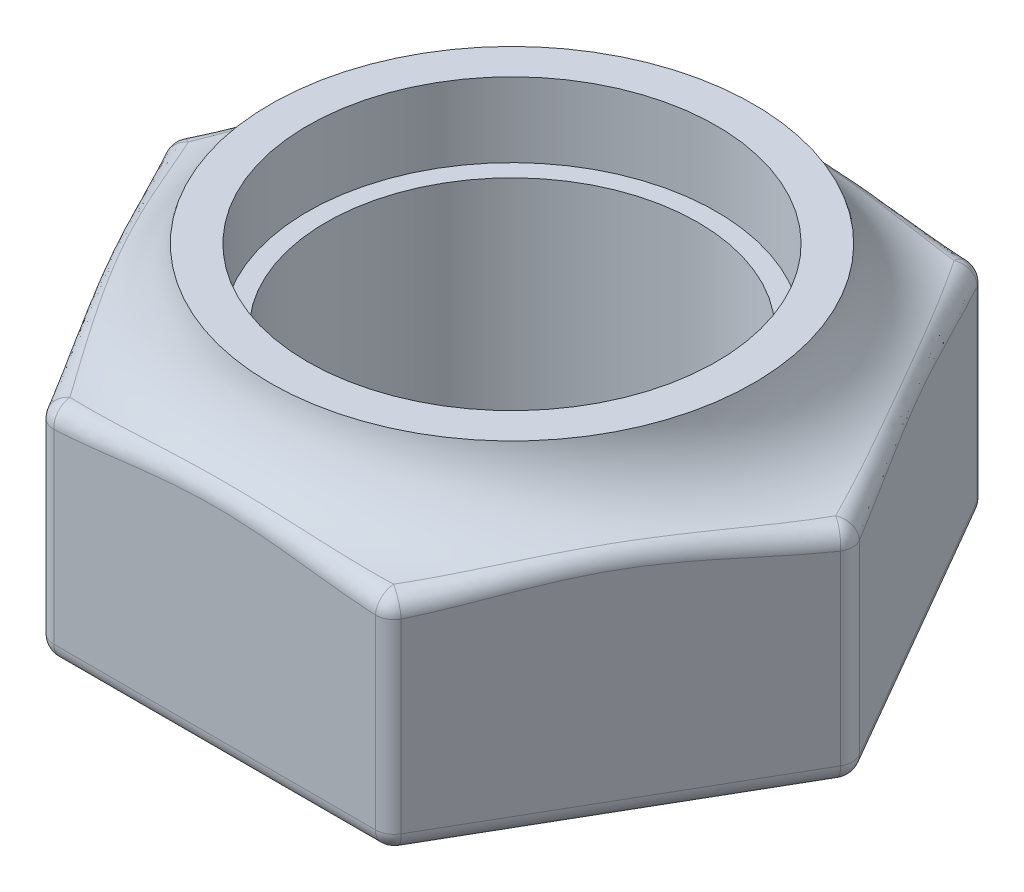
SolidWorks part; units mm, degrees
ref_plane "Front Plane" through (0, 0, 0) normal (0, 0, 1) x (1, 0, 0)
ref_plane "Top Plane" through (0, 0, 0) normal (0, 1, 0) x (1, 0, 0)
ref_plane "Right Plane" through (0, 0, 0) normal (1, 0, 0) x (0, 0, -1)
sketch "Sketch1" plane through (0, 0, 0) normal (0, 1, 0) x (1, 0, 0)
  line L1 (4.6188, 0) -> (2.3094, 4)
  line L2 (2.3094, 4) -> (-2.3094, 4)
  line L3 (-2.3094, 4) -> (-4.6188, 0)
  line L4 (-4.6188, 0) -> (-2.3094, -4)
  line L5 (-2.3094, -4) -> (2.3094, -4)
  line L6 (2.3094, -4) -> (4.6188, 0)
  circle A0 centre (0, 0) radius 4 construction
  point P1 (0, 0)
  dimension "D1" = 8
extrude "Boss-Extrude1" add sketch "Sketch1" along normal blind 3
sketch "Sketch2" plane through (0, 3, 0) normal (0, 1, 0) x (1, 0, 0)
  circle A0 centre (0, 0) radius 2.75
  circle A1 centre (0, 0) radius 3.25
  dimension "D1" = 5.5
  dimension "D2" = 0.5
extrude "Boss-Extrude2" add sketch "Sketch2" along normal blind 1
fillet "Fillet2" radius 1.27 1 edges at (0, 3, 3.25)
sketch "Sketch3" plane through (0, 3, 0) normal (0, 1, 0) x (1, 0, 0)
  circle A0 centre (0, 0) radius 2.5
  dimension "D1" = 5
extrude "Cut-Extrude1" cut sketch "Sketch3" against normal through all
fillet "Fillet3" radius 0.254 18 edges at (-3.215, 3.0863, -2.4315) (-3.4641, 0, -2) (-4.6188, 1.5, 0) (-3.7132, 3.0863, 1.5685) (-3.4641, 0, 2) (-2.3094, 1.5, 4) (-0.4982, 3.0863, 4) (0, 0, 4) (2.3094, 1.5, 4) (3.215, 3.0863, 2.4315) (3.4641, 0, 2) (4.6188, 1.5, 0) (3.7132, 3.0863, -1.5685) (3.4641, 0, -2) (2.3094, 1.5, -4) (0.4982, 3.0863, -4) (-2.3094, 1.5, -4) (0, 0, -4)
